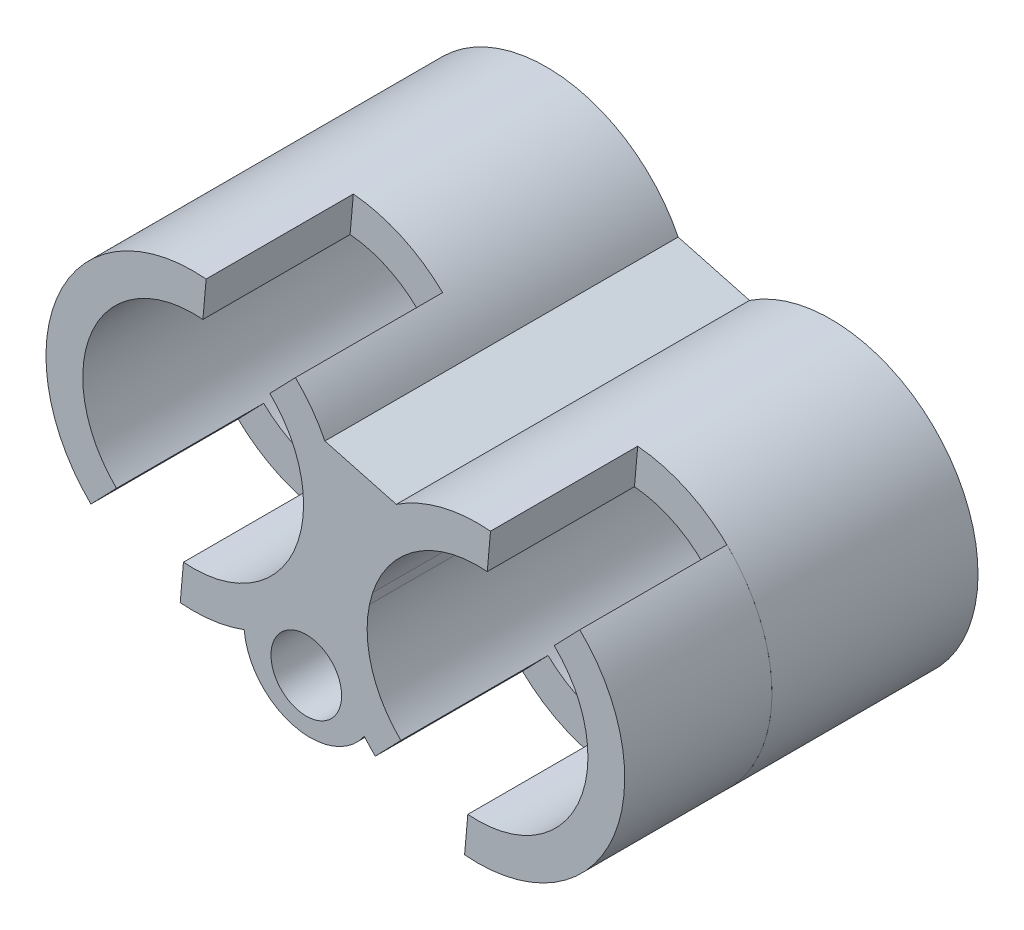
SolidWorks part; units mm, degrees
material "ABS"
ref_plane "Front Plane" through (0, 0, 0) normal (0, 0, 1) x (1, 0, 0)
ref_plane "Top Plane" through (0, 0, 0) normal (0, 1, 0) x (1, 0, 0)
ref_plane "Right Plane" through (0, 0, 0) normal (1, 0, 0) x (0, 0, -1)
sketch "Sketch1" plane through (0, 0, 0) normal (0, 0, 1) x (1, 0, 0)
  circle A0 centre (0, 0) radius 3.285
  circle A1 centre (0, 0) radius 10
  circle A2 centre (0, 0) radius 7.5
  circle A3 centre (19.3185, -5.1764) radius 3.285
  circle A4 centre (19.3185, -5.1764) radius 10
  circle A5 centre (19.3185, -5.1764) radius 7.5
  dimension "D1" = 6.57
  dimension "D2" = 20
  dimension "D3" = 15
  dimension "D4" = 2
extrude "Boss-Extrude1" add sketch "Sketch1" along normal blind 2 contours A2 A0 | A4 | A5 A3 region at (-7.2879, 0, 0) region at (12.0306, -5.1764, 0)
extrude "Boss-Extrude2" add sketch "Sketch1<3>" along normal blind 14 contours A1 A2 | A4 A5 region at (9.634, -1.2683, 0) region at (20.5869, 4.4576, 0)
sketch "Sketch1<3>" plane through (0, 0, 0) normal (0, 0, 1) x (1, 0, 0) same geometry as "Sketch1"
sketch "Sketch2" plane through (0, 0, 14) normal (0, 0, 1) x (1, 0, 0)
  line L0 (-6.946, -7.194) -> (-5.2095, -5.3955)
  line L1 (5.2095, 5.3955) -> (6.946, 7.194)
  line L2 (0.6605, 7.4709) -> (0.8807, 9.9611)
  line L3 (-0.6605, -7.4709) -> (-0.8807, -9.9611)
  line L4 (0.6605, 7.4709) -> (5.2095, 5.3955) construction
  line L5 (-5.2095, -5.3955) -> (-0.6605, -7.4709) construction
  line L6 (12.3725, -12.3704) -> (14.109, -10.5719)
  line L7 (24.528, 0.2191) -> (26.2645, 2.0176)
  line L8 (19.9791, 2.2945) -> (20.1992, 4.7848)
  line L9 (18.658, -12.6472) -> (18.4378, -15.1375)
  line L10 (19.9791, 2.2945) -> (24.528, 0.2191) construction
  line L11 (14.109, -10.5719) -> (18.658, -12.6472) construction
  circle A0 centre (0, 0) radius 10 construction
  circle A1 centre (0, 0) radius 7.5 construction
  circle A2 centre (0, 0) radius 10
  circle A3 centre (0, 0) radius 7.5
  circle A4 centre (19.3185, -5.1764) radius 10
  circle A5 centre (19.3185, -5.1764) radius 7.5
  circle M1 centre (0, 0) radius 7.5
  circle M2 centre (0, 0) radius 10
  dimension "D1" = 5
  dimension "D2" = 5
  dimension "D3" = 2
extrude "Boss-Extrude3" add sketch "Sketch2" along normal blind 10 contours L2 L0 M1 M2 | L3 L1 M1 M2 | A5 L8 A4 L6 | A5 L9 A4 L7 region at (-8.9128, 4.0663, 14) region at (13.7032, 2.851, 14) region at (-0.5679, -8.7339, 14) region at (28.3361, -1.3482, 14)
sketch "Sketch4" plane through (0, 0, 24) normal (0, 0, 1) x (1, 0, 0)
  line L0 (13.8007, 3.1635) -> (8.9485, 4.4637)
  line L1 (8.9485, 4.4637) -> (5.5178, -8.3399)
  line L2 (5.5178, -8.3399) -> (10.37, -9.64)
  line L3 (10.37, -9.64) -> (13.8007, 3.1635)
  arc A0 (20.1992, 4.7848) -> (12.3725, -12.3704) centre (19.3185, -5.1764) ccw construction
  arc A1 (-0.8807, -9.9611) -> (6.946, 7.194) centre (0, 0) ccw construction
  point P0 (13.8007, 3.1635)
  point P1 (8.9485, 4.4637)
  point P5 (5.5178, -8.3399)
  point P9 (10.37, -9.64)
extrude "Boss-Extrude4" add sketch "Sketch4" against normal blind 24
sketch "Sketch5" plane through (0, 0, 24) normal (0, 0, 1) x (1, 0, 0)
  line L0 (5.5178, -8.3399) -> (10.37, -9.64) construction
  circle A0 centre (7.9439, -8.99) radius 4.4969
  point P0 (7.9439, -8.99)
extrude "Boss-Extrude5" add sketch "Sketch5" against normal blind 24
sketch "Sketch6" plane through (0, 0, 24) normal (0, 0, 1) x (1, 0, 0)
  line L0 (11.3746, 3.8136) -> (6.78, -13.3336) construction
  line L1 (13.8007, 3.1635) -> (8.9485, 4.4637) construction
  circle A0 centre (7.6851, -9.9559) radius 2.4
  arc A1 (3.464, -9.3809) -> (11.6281, -11.5684) centre (7.9439, -8.99) ccw construction
  dimension "D1" = 4.8
  dimension "D2" = 1
extrude "Cut-Extrude1" cut sketch "Sketch6" against normal blind 10
